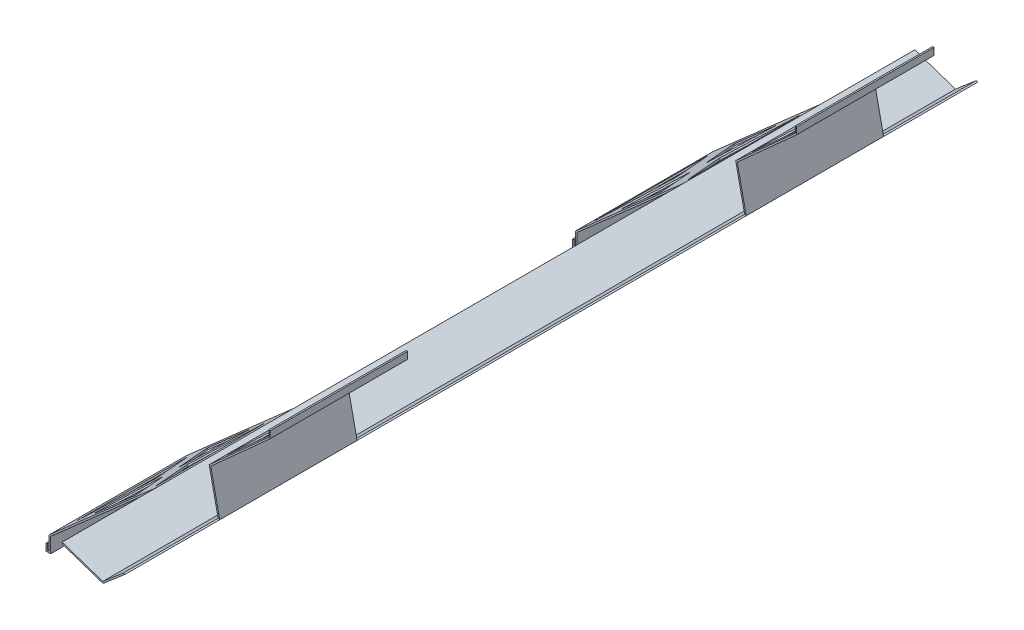
SolidWorks part; units mm, degrees
ref_plane "Front Plane" through (0, 0, 0) normal (0, 0, 1) x (1, 0, 0)
ref_plane "Top Plane" through (0, 0, 0) normal (0, 1, 0) x (1, 0, 0)
ref_plane "Right Plane" through (0, 0, 0) normal (1, 0, 0) x (0, 0, -1)
sketch "Sketch1" plane through (0, 0, 0) normal (0, 0, 1) x (1, 0, 0)
  line L0 (11, 5) -> (11, 55)
  line L1 (11, 55) -> (386.1701, 385.5259)
  line L2 (386.1701, 385.5259) -> (528.3188, 337.6327)
  line L3 (528.3188, 337.6327) -> (601.4994, 400.355)
  line L4 (601.4994, 400.355) -> (570.3532, 547.0857)
  line L5 (570.3532, 547.0857) -> (778.4856, 734.3848)
  line L11 (607.0067, 398.49) -> (529.4152, 331.9872)
  line L12 (529.4152, 331.9872) -> (387.3094, 379.8659)
  line L13 (387.3094, 379.8659) -> (16, 52.7414)
  line L14 (16, 52.7414) -> (16, 0)
  line L16 (11, 5) -> (5, 5)
  line L20 (5, 5) -> (5, 25)
  line L21 (5, 25) -> (0, 25)
  line L22 (0, 25) -> (0, 0)
  line L23 (0, 0) -> (16, 0)
  line L24 (575.8437, 545.3001) -> (607.0067, 398.49)
  line L25 (778.4856, 734.3848) -> (778.5497, 756.6504)
  line L26 (778.5497, 756.6504) -> (783.5497, 756.6215)
  line L28 (783.5497, 756.6215) -> (783.3785, 732.0614)
  line L29 (575.8437, 545.3001) -> (783.3785, 732.0614)
  point P2 (778.9065, 696.2291)
  point P10 (0, 0)
  point P24 (765.1212, 685.3907)
  point P25 (778.0808, 697.4046)
  point P26 (778.9065, 697.4046)
  point P27 (778.9065, 697.7837)
  point P28 (778.6584, 697.9039)
  point P29 (778.9065, 698.1709)
  point P30 (0, 0)
  dimension "D1" = 5
  dimension "D2" = 5
  dimension "D3" = 5
  dimension "D4" = 5
  dimension "D5" = 5
  dimension "D6" = 120
  dimension "D7" = 120
  dimension "D8" = 5
  dimension "D9" = 500
  dimension "D10" = 280
  dimension "D11" = 245
  dimension "D12" = 150
  dimension "D13" = 5
  dimension "D14" = 150
  dimension "D15" = 6
  dimension "D16" = 50
  dimension "D17" = 25
extrude "Boss-Extrude1" add sketch "Sketch1" along normal blind 480
sketch "Sketch2" plane through (-16.8178, 18.6885, 0) normal (-0.6689, 0.7433, 0) x (0.7433, 0.6689, 0)
  line L0 (194.9675, -40) -> (394.9397, -40)
  line L1 (394.9397, -40) -> (294.9536, -213.181)
  line L2 (294.9536, -213.181) -> (194.9675, -40)
  line L3 (544.9397, 0) -> (44.9675, 0) construction
  line L4 (544.9397, -480) -> (544.9397, 0) construction
  line L5 (44.9675, -480) -> (44.9675, 0) construction
  line L6 (126.6736, -240) -> (507.7402, -240) construction
  line L7 (544.9397, -480) -> (44.9675, -480) construction
  line L8 (394.9397, -440) -> (294.9536, -266.819)
  line L9 (194.9675, -440) -> (394.9397, -440)
  line L10 (294.9536, -266.819) -> (194.9675, -440)
  line L11 (78.3878, -38.0781) -> (78.3878, -441.9219)
  line L12 (78.3878, -441.9219) -> (194.9675, -240)
  line L13 (194.9675, -240) -> (78.3878, -38.0781)
  line L14 (294.9536, -14.6562) -> (294.9536, -467.4989) construction
  line L15 (511.5194, -441.9219) -> (394.9397, -240)
  line L16 (511.5194, -38.0781) -> (511.5194, -441.9219)
  line L17 (394.9397, -240) -> (511.5194, -38.0781)
  line L18 (808.3952, -38.0781) -> (1044.6924, -38.0781)
  line L19 (1044.6924, -38.0781) -> (926.5438, -185.2793)
  line L20 (926.5438, -185.2793) -> (808.3952, -38.0781)
  line L21 (1044.6924, -441.9219) -> (926.5438, -294.7207)
  line L22 (808.3952, -441.9219) -> (1044.6924, -441.9219)
  line L23 (926.5438, -294.7207) -> (808.3952, -441.9219)
  dimension "D1" = 40
  dimension "D2" = 60
  dimension "D3" = 60
  dimension "D4" = 150
  dimension "D5" = 150
  dimension "D6" = 240
  dimension "D7" = 51.248
  dimension "D8" = 51.248
extrude "Cut-Extrude3" cut sketch "Sketch2" against normal blind 505 and the other way blind 505
sketch "Sketch3" plane through (0, 0, 480) normal (0, 0, 1) x (1, 0, 0)
  line L0 (386.1701, 385.5259) -> (528.3188, 337.6327)
  line L1 (528.3188, 337.6327) -> (601.4994, 400.355)
  line L5 (607.0067, 398.49) -> (529.4152, 331.9872)
  line L6 (529.4152, 331.9872) -> (387.3094, 379.8659)
  line L7 (387.3094, 379.8659) -> (386.1701, 385.5259)
  line L8 (601.4994, 400.355) -> (607.0067, 398.49)
extrude "Boss-Extrude2" add sketch "Sketch3" along normal blind 1360 and the other way blind 810
sketch "Sketch4" plane through (0, 0, 1840) normal (0, 0, 1) x (1, 0, 0)
  line L0 (0, 25) -> (5, 25)
  line L1 (5, 25) -> (5, 5)
  line L2 (5, 5) -> (11, 5)
  line L3 (11, 5) -> (11, 55)
  line L4 (11, 55) -> (386.1701, 385.5259)
  line L5 (386.1701, 385.5259) -> (528.3188, 337.6327)
  line L6 (528.3188, 337.6327) -> (601.4994, 400.355)
  line L7 (601.4994, 400.355) -> (570.3532, 547.0857)
  line L8 (570.3532, 547.0857) -> (778.4856, 734.3848)
  line L9 (778.4856, 734.3848) -> (778.5497, 756.6504)
  line L10 (778.5497, 756.6504) -> (783.5497, 756.6215)
  line L11 (783.5497, 756.6215) -> (783.3785, 732.0614)
  line L12 (783.3785, 732.0614) -> (575.8437, 545.3001)
  line L13 (575.8437, 545.3001) -> (607.0067, 398.49)
  line L14 (607.0067, 398.49) -> (529.4152, 331.9872)
  line L15 (529.4152, 331.9872) -> (387.3094, 379.8659)
  line L16 (387.3094, 379.8659) -> (16, 52.7414)
  line L17 (16, 52.7414) -> (16, 0)
  line L18 (16, 0) -> (0, 0)
  line L19 (0, 0) -> (0, 25)
extrude "Boss-Extrude3" add sketch "Sketch4" along normal blind 480
sketch "Sketch5" plane through (0, 0, 2320) normal (0, 0, 1) x (1, 0, 0)
  line L0 (386.1701, 385.5259) -> (528.3188, 337.6327)
  line L1 (528.3188, 337.6327) -> (601.4994, 400.355)
  line L2 (601.4994, 400.355) -> (607.0067, 398.49)
  line L3 (607.0067, 398.49) -> (529.4152, 331.9872)
  line L4 (529.4152, 331.9872) -> (387.3094, 379.8659)
  line L5 (387.3094, 379.8659) -> (386.1701, 385.5259)
extrude "Boss-Extrude4" add sketch "Sketch5" along normal blind 330
sketch "Sketch6" plane through (-22.4739, 25.5094, 0) normal (-0.6611, 0.7503, 0) x (0.7503, 0.6611, 0)
  line L0 (194.6116, -1880) -> (394.6116, -1880)
  line L1 (394.6116, -1880) -> (294.6116, -2053.2051)
  line L2 (294.6116, -2053.2051) -> (194.6116, -1880)
  line L3 (544.6116, -2320) -> (544.6116, -1840) construction
  line L4 (44.6116, -2320) -> (44.6116, -1840) construction
  line L5 (111.9768, -2080) -> (494.1342, -2080) construction
  line L6 (544.6116, -1840) -> (44.6116, -1840) construction
  line L7 (544.6116, -2320) -> (44.6116, -2320) construction
  line L8 (294.6116, -2106.7949) -> (194.6116, -2280)
  line L9 (194.6116, -2280) -> (394.6116, -2280)
  line L10 (394.6116, -2280) -> (294.6116, -2106.7949)
  line L11 (294.6116, -1778.362) -> (294.6116, -2354.8368) construction
  line L12 (108.7384, -1882.7969) -> (222.5937, -2080)
  line L13 (222.5937, -2080) -> (108.7384, -2277.2031)
  line L14 (108.7384, -2277.2031) -> (108.7384, -1882.7969)
  line L15 (366.6295, -2080) -> (480.4848, -2277.2031)
  line L16 (480.4848, -1882.7969) -> (366.6295, -2080)
  line L17 (480.4848, -2277.2031) -> (480.4848, -1882.7969)
  line L18 (806.7817, -1884.9121) -> (1051.5863, -1884.9121)
  line L19 (1051.5863, -1884.9121) -> (929.184, -2037.4222)
  line L20 (929.184, -2037.4222) -> (806.7817, -1884.9121)
  line L26 (806.7817, -2275.0879) -> (1051.5863, -2275.0879)
  line L27 (1051.5863, -2275.0879) -> (929.184, -2122.5778)
  line L28 (929.184, -2122.5778) -> (806.7817, -2275.0879)
  point P20 (804.554, -1882.1365)
  point P28 (1051.5863, -1884.9121)
  dimension "D1" = 150
  dimension "D2" = 60
  dimension "D3" = 60
  dimension "D4" = 150
  dimension "D5" = 40
  dimension "D6" = 240
  dimension "D10" = 51.25
  dimension "D11" = 51.25
extrude "Cut-Extrude4" cut sketch "Sketch6" against normal blind 330 and the other way blind 330
